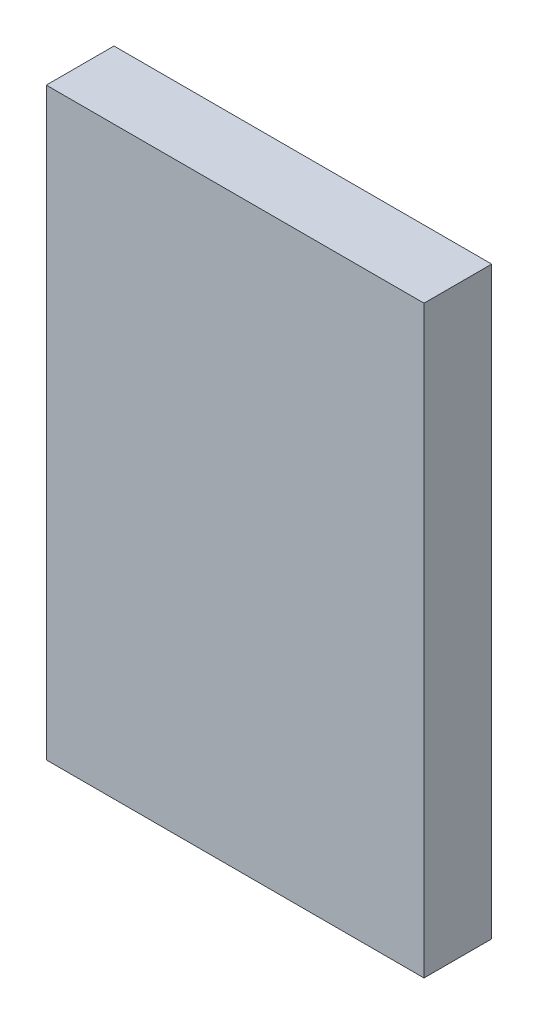
SolidWorks part; units mm, degrees
material "ﾎﾟﾘｵｷｼﾒﾁﾚﾝ(POM)ｱｾﾀｰﾙ共重合体"
ref_plane "正面" through (0, 0, 0) normal (0, 0, 1) x (1, 0, 0)
ref_plane "平面" through (0, 0, 0) normal (0, 1, 0) x (1, 0, 0)
ref_plane "右側面" through (0, 0, 0) normal (1, 0, 0) x (0, 0, -1)
sketch "ｽｹｯﾁ1" plane through (0, 0, 0) normal (0, 0, 1) x (1, 0, 0)
  line L0 (-0.75, 68.75) -> (0, 68.75)
  line L1 (0, 0) -> (53, 0)
  line L2 (0, 0) -> (0, 82)
  line L3 (0, 82) -> (53, 82)
  line L4 (53, 0) -> (53, 82)
  line L5 (-0.75, 67.25) -> (0, 67.25)
  line L6 (-0.75, 14.75) -> (0, 14.75)
  line L7 (-0.75, 13.25) -> (0, 13.25)
  line L8 (7.25, -0.75) -> (7.25, 0)
  line L9 (8.75, -0.75) -> (8.75, 0)
  line L10 (25.75, -0.75) -> (25.75, 0)
  line L11 (27.25, -0.75) -> (27.25, 0)
  line L12 (44.25, -0.75) -> (44.25, 0)
  line L13 (45.75, -0.75) -> (45.75, 0)
  arc A0 (-0.75, 14.75) -> (-0.75, 13.25) centre (-0.75, 14) ccw
  arc A1 (-0.75, 68.75) -> (-0.75, 67.25) centre (-0.75, 68) ccw
  arc A2 (7.25, -0.75) -> (8.75, -0.75) centre (8, -0.75) ccw
  arc A3 (25.75, -0.75) -> (27.25, -0.75) centre (26.5, -0.75) ccw
  arc A4 (44.25, -0.75) -> (45.75, -0.75) centre (45, -0.75) ccw
  point P16 (26.5, 0)
  dimension "D4" = 1.5
  dimension "D6" = 1.5
  dimension "D1" = 53
  dimension "D2" = 82
  dimension "D3" = 14
  dimension "D5" = 14
  dimension "D7" = 8
  dimension "D8" = 8
extrude "ﾎﾞｽ - 押し出し1" add sketch "ｽｹｯﾁ1" along normal blind 9.5 contours L1 L4 L3 L2 region at (26.5, 41, 0)
extrude "ﾎﾞｽ - 押し出し2" add sketch "ｽｹｯﾁ1<3>" along normal blind 5.5 contours L0 A1 L5 L2 | L6 A0 L7 L2 | L8 A2 L9 L1 | L10 A3 L11 L1 | L12 A4 L13 L1 region at (-0.68, 68, 0) region at (-0.68, 14, 0) region at (45, -0.68, 0) region at (8, -0.68, 0) region at (26.5, -0.68, 0)
sketch "ｽｹｯﾁ1<3>" plane through (0, 0, 0) normal (0, 0, 1) x (1, 0, 0) same geometry as "ｽｹｯﾁ1"
